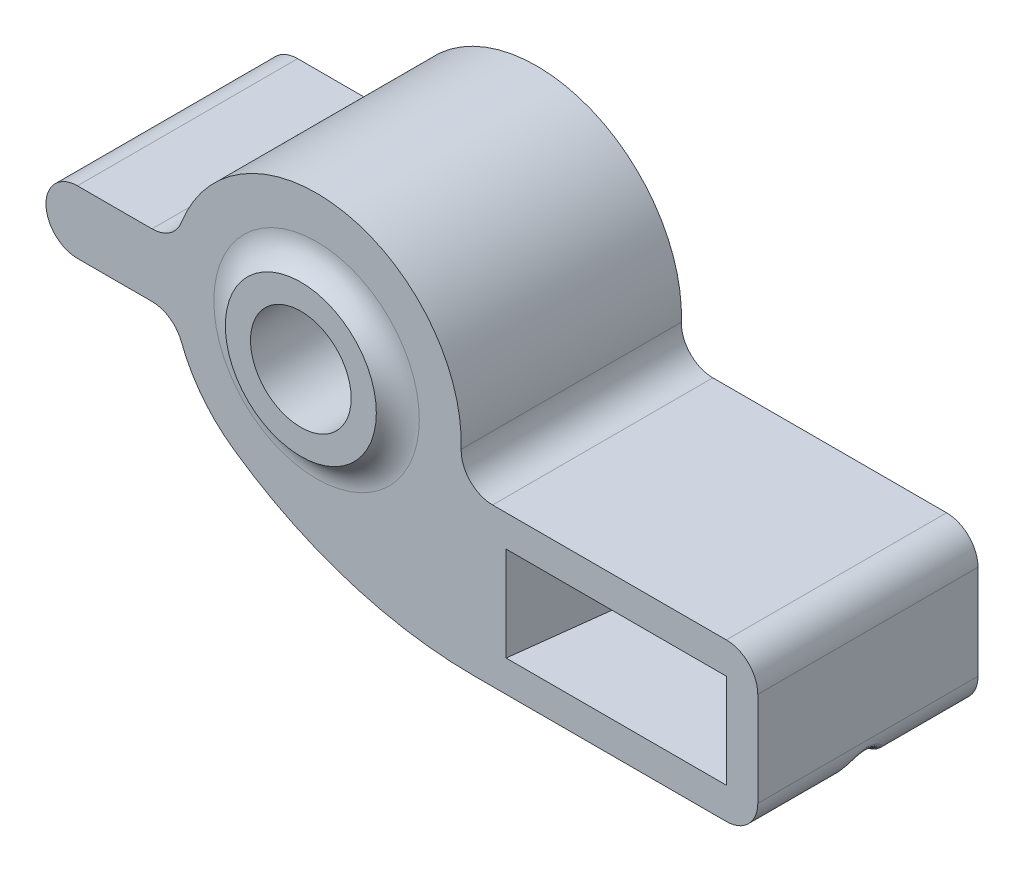
SolidWorks part; units mm, degrees
ref_plane "Front Plane" through (0, 0, 0) normal (0, 0, 1) x (1, 0, 0)
ref_plane "Top Plane" through (0, 0, 0) normal (0, 1, 0) x (1, 0, 0)
ref_plane "Right Plane" through (0, 0, 0) normal (1, 0, 0) x (0, 0, -1)
sketch "Sketch1" plane through (0, 0, 0) normal (0, 0, 1) x (1, 0, 0)
  circle A0 centre (0, 0) radius 1.6
  circle A1 centre (0, 0) radius 4.6
  dimension "D1" = 3.2
  dimension "D2" = 3
extrude "Boss-Extrude1" add sketch "Sketch1" along normal mid plane 7
sketch "Sketch2" plane through (0, 0, 0) normal (0, 0, 1) x (1, 0, 0)
  line L1 (6.025, -5.1875) -> (13.025, -5.1875)
  line L2 (6.025, -5.1875) -> (6.025, -2.1875)
  line L3 (6.025, -2.1875) -> (13.025, -2.1875)
  line L4 (13.025, -5.1875) -> (13.025, -2.1875)
  line L5 (14.025, -6.1875) -> (5.025, -6.1875)
  line L7 (5.025, -6.1875) -> (6.025, -5.1875) construction
  line L8 (13.025, -5.1875) -> (14.025, -6.1875) construction
  line L9 (14.025, -6.1875) -> (14.025, -1.1875)
  line L10 (14.025, -1.1875) -> (5.5969, -1.1875)
  line L11 (13.025, -2.1875) -> (14.025, -1.1875) construction
  arc A0 (-2.6427, -3.7651) -> (4.5974, -0.154) centre (0, 0) ccw
  circle A1 centre (0, 0) radius 4.6 construction
  arc A2 (5.5969, -1.1875) -> (4.5974, -0.154) centre (5.5969, -0.1875) cw
  arc A3 (-2.6427, -3.7651) -> (5.025, -6.1875) centre (5.025, 7.1592) ccw
  point P16 (9.525, -2.1875)
  point P18 (0, -4.6)
  dimension "D4" = 1
  dimension "D1" = 3
  dimension "D2" = 1.5875
  dimension "D3" = 7
  dimension "D5" = 9.525
  dimension "D6" = 1
extrude "Boss-Extrude2" add sketch "Sketch2" along normal mid plane 7
sketch "Sketch3" plane through (0, -5.1875, 0) normal (0, 1, 0) x (1, 0, 0)
  line L0 (6.025, -3.5) -> (13.025, 3.5) construction
  line L1 (6.4975, 0.3697) -> (6.025, -3.5)
  line L2 (12.5525, 0.3697) -> (13.025, -3.5)
  line L3 (8.025, 3.5) -> (8.025, 2.6557)
  line L4 (13.025, 3.5) -> (6.025, 3.5)
  line L5 (6.025, 3.5) -> (6.025, -3.5)
  line L6 (6.025, -3.5) -> (13.025, -3.5)
  line L7 (13.025, -3.5) -> (13.025, 3.5)
  line L8 (13.025, 3.5) -> (11.025, 3.5)
  line L9 (6.025, 3.5) -> (6.025, -3.5)
  line L10 (6.025, -3.5) -> (13.025, -3.5) construction
  line L11 (13.025, -3.5) -> (13.025, 3.5)
  line L12 (11.025, 3.5) -> (11.025, 2.6557)
  line L13 (8.025, 3.5) -> (6.025, 3.5)
  arc A0 (12.5525, 0.3697) -> (11.025, 2.6557) centre (9.525, 0) ccw
  arc A1 (8.025, 2.6557) -> (6.4975, 0.3697) centre (9.525, 0) ccw
  dimension "D2" = 6.1
  dimension "D3" = 3
  dimension "D1" = 0
extrude "Boss-Extrude3" add sketch "Sketch3" along normal up to next
fillet "Fillet5" radius 1 2 edges at (14.025, -6.1875, 0) (14.025, -1.1875, 0)
sketch "Sketch6" plane through (14.025, 0, 0) normal (1, 0, 0) x (0, 0, -1)
  line L1 (-3.5, -6.1875) -> (3.5, -6.1875) construction
  circle A0 centre (0, -6.1875) radius 0.625
  dimension "D1" = 1.25
extrude "Cut-Extrude1" cut sketch "Sketch6" against normal through all
fillet "Fillet1" radius 0.2 4 edges at (9.025, -6.1875, -0.625) (0.9887, -5.5625, -0.0069) (9.025, -6.1875, 0.625) (13.9515, -5.5639, -0.0417)
sketch "Sketch7" plane through (0, 0, 0) normal (0, 0, 1) x (1, 0, 0)
  line L0 (-4.6, 0) -> (-7.6, 0) construction
  line L1 (-4.6, -1) -> (-7.6, -1)
  line L2 (-4.6, 1) -> (-7.6, 1)
  arc A0 (4.5974, -0.154) -> (-2.6427, -3.7651) centre (0, 0) ccw construction
  arc A1 (-4.6, -1) -> (-4.6, 1) centre (-4.6, 0) ccw
  arc A2 (-7.6, 1) -> (-7.6, -1) centre (-7.6, 0) ccw
  point P7 (-6.1, 0)
  dimension "D1" = 2
  dimension "D2" = 3
extrude "Boss-Extrude4" add sketch "Sketch7" along normal mid plane 7
fillet "Fillet2" radius 1 2 edges at (-4.4913, 0.9941, 0) (-4.4913, -0.9941, 0)
fillet "Fillet3" radius 1 2 edges at (11.025, -3.6875, -2.6557) (8.025, -3.6875, -2.6557)
extrude "Boss-Extrude5" add sketch "Sketch1<2>" along normal mid plane 1 from surface starting at face at (2.3023, -1.6576, 3.5)
sketch "Sketch1<2>" plane through (0, 0, 0) normal (0, 0, 1) x (1, 0, 0) same geometry as "Sketch1"
sketch "Sketch9" plane through (0, 0, 4) normal (0, 0, 1) x (1, 0, 0)
  circle A0 centre (0, 0) radius 2.4
  circle A1 centre (0, 0) radius 1.6 construction
  dimension "D1" = 0.8
extrude "Cut-Extrude2" cut sketch "Sketch9" against normal up to surface (0.5 mm away) flip side to cut up to face at (-5.893, 0, 3.5)
fillet "Fillet4" radius 1 1 edges at (2.4, 0, 3.5)
equation "\"thickmess\"= 7mm"
equation "\"D1@Boss-Extrude1\"=\"thickmess\""
equation "\"D1@Boss-Extrude2\"=\"thickmess\""
equation "\"D1@Boss-Extrude4\"=\"thickmess\""
